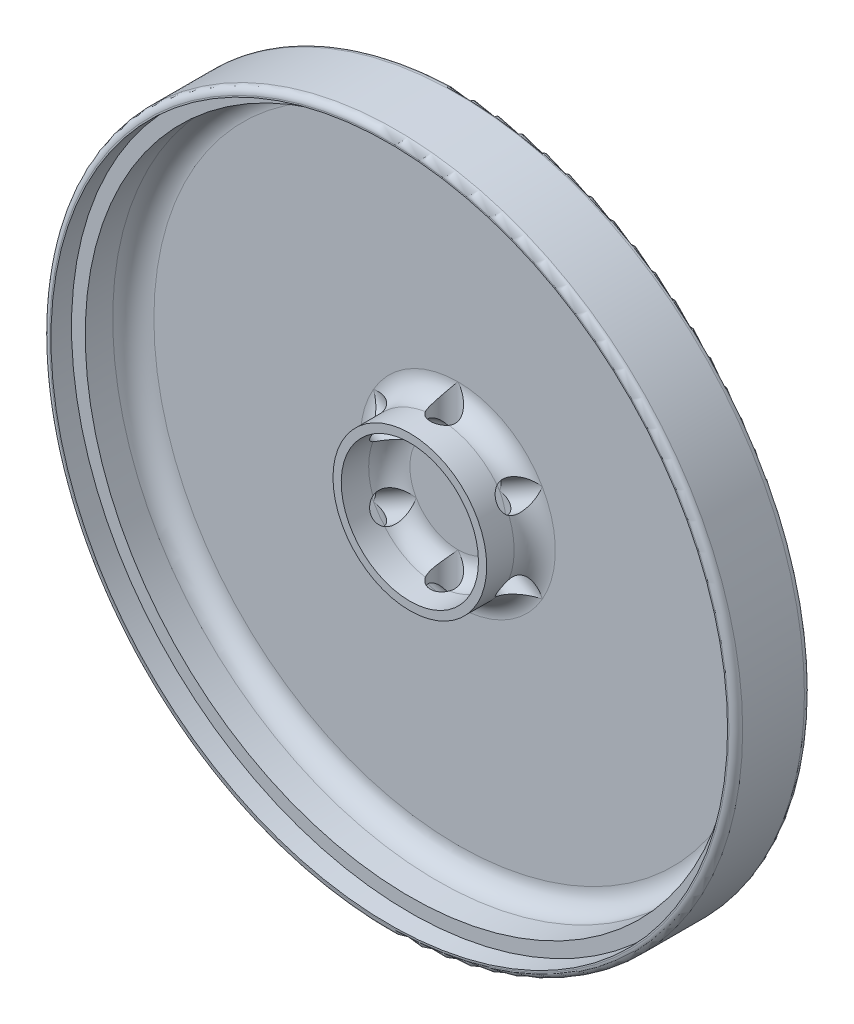
SolidWorks part; units mm, degrees
note: The reader was unsure of these and kept them because the rebuilt part matched: shared geometry of "Sketch1<3>", "Sketch1<4>", "Sketch1<5>".
ref_plane "Front Plane" through (0, 0, 0) normal (0, 0, 1) x (1, 0, 0)
ref_plane "Top Plane" through (0, 0, 0) normal (0, 1, 0) x (1, 0, 0)
ref_plane "Right Plane" through (0, 0, 0) normal (1, 0, 0) x (0, 0, -1)
sketch "Sketch1" plane through (0, 0, 0) normal (0, 0, 1) x (1, 0, 0)
  circle A0 centre (0, 0) radius 50.5
  circle A1 centre (0, 0) radius 49.3
  circle A2 centre (0, 0) radius 47.3
  circle A3 centre (0, 0) radius 10
  circle A4 centre (0, 0) radius 11.2
  dimension "D1" = 101
  dimension "D5" = 20
  dimension "D2" = 1.2
  dimension "D3" = 2
  dimension "D4" = 1.2
extrude "Boss-Extrude1" add sketch "Sketch1" against normal blind 1 contours A2 A4 | A1 A2 | A0 A1 | A3 | A4 A3
extrude "Boss-Extrude2" add sketch "Sketch1<3>" along normal blind 10 contours A0 A1
sketch "Sketch1<3>" plane through (0, 0, 0) normal (0, 0, 1) x (1, 0, 0) same geometry as "Sketch1"
extrude "Boss-Extrude3" add sketch "Sketch1<4>" along normal blind 7 contours A1 A2
sketch "Sketch1<4>" plane through (0, 0, 0) normal (0, 0, 1) x (1, 0, 0) same geometry as "Sketch1"
extrude "Boss-Extrude4" add sketch "Sketch1<5>" along normal blind 7 contours A4 A3
sketch "Sketch1<5>" plane through (0, 0, 0) normal (0, 0, 1) x (1, 0, 0) same geometry as "Sketch1"
sketch "Sketch2" plane through (0, 0, 0) normal (0, 1, 0) x (1, 0, 0)
  line L2 (-10, 0) -> (10, 0) construction
  circle A0 centre (0, -2) radius 2
  dimension "D1" = 4
extrude "Cut-Extrude3" cut sketch "Sketch2" against normal up to next and the other way up to next
fillet "Fillet1" radius 3 1 edges at (47.3, 0, 0)
fillet "Fillet2" radius 3 8 edges at (10, 0, 0) (-11.2, 0, 0) (-0.4244, 11.192, 3.9544) (-0.4155, 9.9914, 3.9564) (-10, 0, 0) (11.2, 0, 0) (0, -11.2, 4) (0, -10, 4)
fillet "Fillet3" radius 1 1 edges at (50.5, 0, -1)
fillet "Fillet4" radius 1 1 edges at (50.5, 0, 10)
pattern_circular "CirPattern1" count 3 over 360 about axis through (0, 0, 7) along (0, 0, -1) of "Cut-Extrude3"
